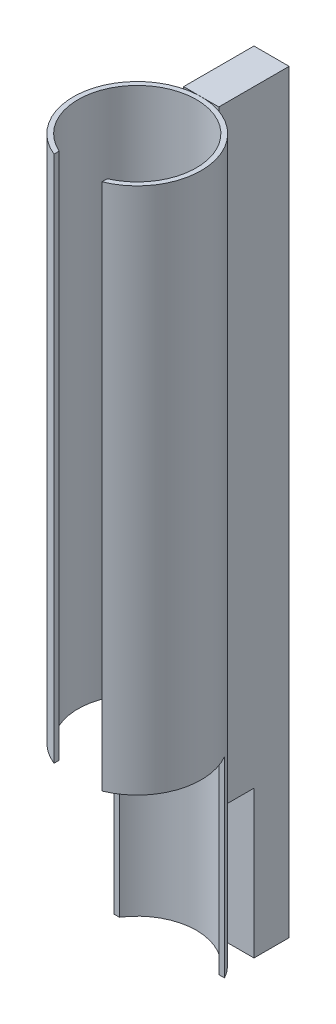
SolidWorks part; units mm, degrees
ref_plane "Plan de face" through (0, 0, 0) normal (0, 0, 1) x (1, 0, 0)
ref_plane "Plan de dessus" through (0, 0, 0) normal (0, 1, 0) x (1, 0, 0)
ref_plane "Plan de droite" through (0, 0, 0) normal (1, 0, 0) x (0, 0, -1)
sketch "Esquisse1" plane through (0, 0, 0) normal (0, 1, 0) x (1, 0, 0)
  circle A0 centre (0, 0) radius 40
  circle A1 centre (0, 0) radius 37
  dimension "D1" = 80
  dimension "D2" = 74
extrude "Boss.-Extru.1" add sketch "Esquisse1" along normal blind 450
sketch "Esquisse2" plane through (0, 0, 0) normal (0, 0, 1) x (1, 0, 0)
  line L0 (40, 0) -> (40, 450) construction
  line L1 (-40, 0) -> (40, 0)
  line L2 (-40, 0) -> (-40, 120)
  line L3 (-40, 120) -> (40, 120)
  line L4 (40, 0) -> (40, 120)
  dimension "D1" = 120
extrude "Enlèv. mat.-Extru.1" cut sketch "Esquisse2" along normal through all and the other way blind 20
sketch "Esquisse3" plane through (0, 0, 0) normal (1, 0, 0) x (0, 0, -1)
  line L0 (62, -22) -> (84, -22)
  line L1 (84, -22) -> (84, 450)
  line L2 (84, 450) -> (40, 450)
  line L3 (40, 450) -> (40, 70)
  line L4 (40, 0) -> (40, 450) construction
  line L5 (40, 70) -> (62, 70)
  line L6 (62, 70) -> (62, -22)
  dimension "D1" = 70
  dimension "D2" = 22
  dimension "D3" = 22
  dimension "D4" = 44
extrude "Boss.-Extru.2" add sketch "Esquisse3" along normal mid plane 22 separate body
sketch "Esquisse4" plane through (0, 0, 0) normal (0, 0, 1) x (1, 0, 0)
  line L1 (-15, 450) -> (15, 450)
  line L2 (-15, 450) -> (-15, 0)
  line L3 (-15, 0) -> (15, 0)
  line L4 (15, 450) -> (15, 0)
  line L5 (40, 450) -> (-40, 450) construction
  dimension "D1" = 30
extrude "Enlèv. mat.-Extru.2" cut sketch "Esquisse4" along normal through all
